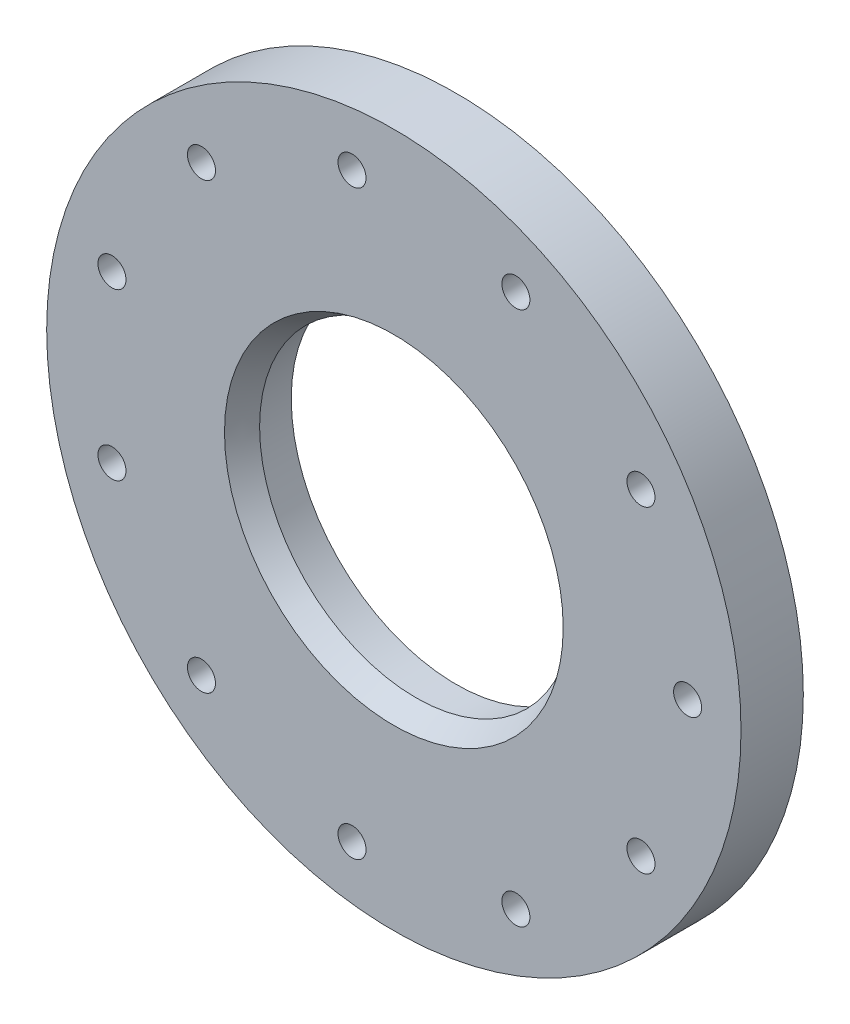
SolidWorks part; units mm, degrees
ref_plane "Front Plane" through (0, 0, 0) normal (0, 0, 1) x (1, 0, 0)
ref_plane "Top Plane" through (0, 0, 0) normal (0, 1, 0) x (1, 0, 0)
ref_plane "Right Plane" through (0, 0, 0) normal (1, 0, 0) x (0, 0, -1)
ref_plane "Plane1" through (0, 0, 15) normal (0, 0, 1) x (1, 0, 0)
sketch "Sketch1" plane through (0, 0, 15) normal (0, 0, 1) x (1, 0, 0)
  circle A0 centre (0, 0) radius 39
  circle A1 centre (0, 0) radius 33 construction
  circle A2 centre (33, 0) radius 2.525
  circle A3 centre (27.7614, -17.8411) radius 2.525
  circle A4 centre (13.7087, -30.0179) radius 2.525
  circle A5 centre (-4.6964, -32.6641) radius 2.525
  circle A6 centre (-21.6104, -24.9397) radius 2.525
  circle A7 centre (-31.6633, -9.2972) radius 2.525
  circle A8 centre (-31.6633, 9.2972) radius 2.525
  circle A9 centre (-21.6104, 24.9397) radius 2.525
  circle A10 centre (-4.6964, 32.6641) radius 2.525
  circle A11 centre (13.7087, 30.0179) radius 2.525
  circle A12 centre (27.7614, 17.8411) radius 2.525
  circle A13 centre (0, 0) radius 16.025
  point P28 (0, 0)
extrude "Boss-Extrude1" add sketch "Sketch1" along normal blind 7
sketch "Sketch2" plane through (0, 0, 15) normal (0, 0, -1) x (-1, 0, 0)
  circle A0 centre (0, 0) radius 18.525
  dimension "D1" = 37.05
extrude "Cut-Extrude1" cut sketch "Sketch2" against normal blind 4.5
sketch "Sketch3" plane through (0, 0, 22) normal (0, 0, 1) x (1, 0, 0)
  circle A0 centre (-4.6964, 32.6641) radius 1.575
  circle A1 centre (-4.6964, 32.6641) radius 2.55
  circle A2 centre (13.7087, 30.0179) radius 2.55
  circle A3 centre (13.7087, 30.0179) radius 1.575
  circle A4 centre (27.7614, 17.8411) radius 2.55
  circle A5 centre (27.7614, 17.8411) radius 1.575
  circle A6 centre (33, 0) radius 2.55
  circle A7 centre (33, 0) radius 1.575
  circle A8 centre (27.7614, -17.8411) radius 2.55
  circle A9 centre (27.7614, -17.8411) radius 1.575
  circle A10 centre (13.7087, -30.0179) radius 2.55
  circle A11 centre (13.7087, -30.0179) radius 1.575
  circle A12 centre (-4.6964, -32.6641) radius 2.55
  circle A13 centre (-4.6964, -32.6641) radius 1.575
  circle A14 centre (-21.6104, -24.9397) radius 2.55
  circle A15 centre (-21.6104, -24.9397) radius 1.575
  circle A16 centre (-31.6633, -9.2972) radius 2.55
  circle A17 centre (-31.6633, -9.2972) radius 1.575
  circle A18 centre (-31.6633, 9.2972) radius 2.55
  circle A19 centre (-31.6633, 9.2972) radius 1.575
  circle A20 centre (-21.6104, 24.9397) radius 2.55
  circle A21 centre (-21.6104, 24.9397) radius 1.575
  point P36 (0, 0)
  dimension "D1" = 5.1
  dimension "D2" = 3.15
  dimension "D3" = 11
extrude "Boss-Extrude2" add sketch "Sketch3" against normal blind 4
chamfer "Chamfer1" distance 3 angle 60 1 edges at (16.025, 0, 22) first distance on face at (39, 0, 22)
chamfer "Chamfer3" distance 0.5 angle 45 11 edges at (35.525, 0, 15) (30.2864, -17.8411, 15) (16.2337, -30.0179, 15) (-2.1714, -32.6641, 15) (-19.0854, -24.9397, 15) (-29.1383, -9.2972, 15) (-29.1383, 9.2972, 15) (-19.0854, 24.9397, 15) (-2.1714, 32.6641, 15) (16.2337, 30.0179, 15) (30.2864, 17.8411, 15)
equation "\"RingPinShaft\"= 5.05"
equation "\"CenterBearingOut\"=32.05"
equation "\"OutputBearingOut\"=37.05"
equation "\"RingPostIn\"=5.15"
equation "\"CamBearingOut\"=15.1"
equation "\"DiskOutputShaft\"=10.1"
equation "\"CenterShaft\"=25.2"
equation "\"Eccentricity\"=2"
equation "\"CycCamShaft\"=10.05"
equation "\"m3Thru\"=3.15"
equation "\"m3Insert\"=4.2"
equation "\"D2@Sketch3\"=\"m3Thru\""
equation "\"D1@Sketch2\"=\"OutputBearingOut\""
